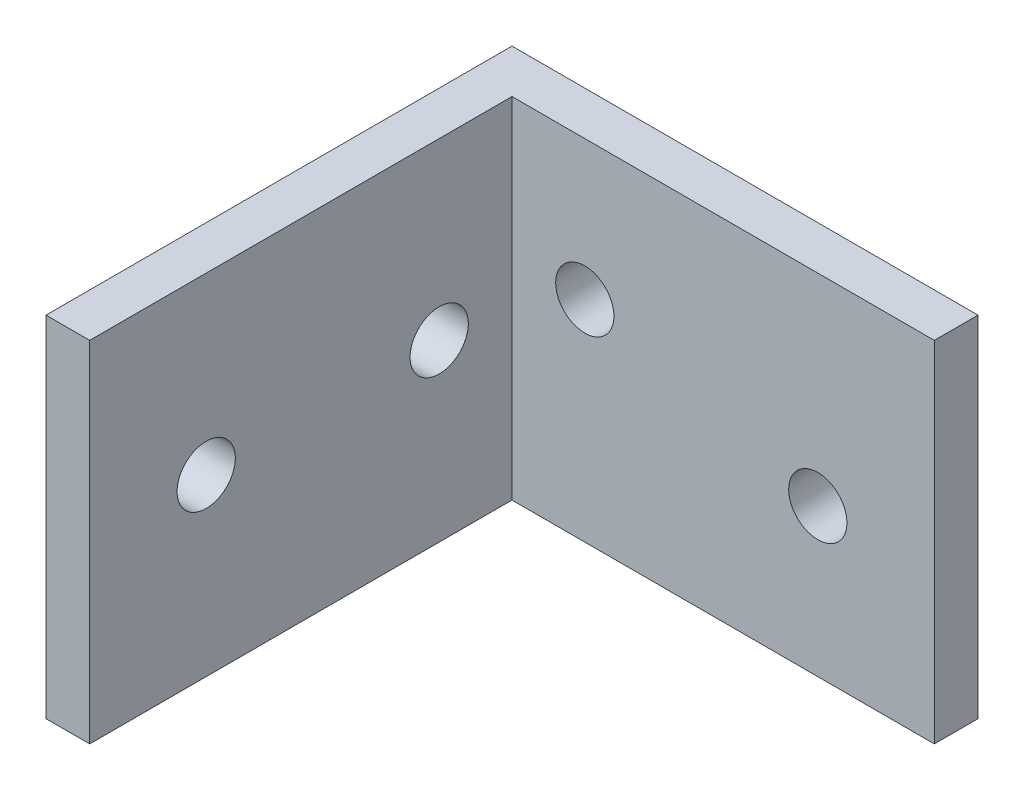
SolidWorks part; units mm, degrees
material "6061 Alloy"
ref_plane "Front Plane" through (0, 0, 0) normal (0, 0, 1) x (1, 0, 0)
ref_plane "Top Plane" through (0, 0, 0) normal (0, 1, 0) x (1, 0, 0)
ref_plane "Right Plane" through (0, 0, 0) normal (1, 0, 0) x (0, 0, -1)
sketch "Sketch1" plane through (0, 0, 0) normal (0, 1, 0) x (1, 0, 0)
  line L0 (0, 0) -> (0, 50.8)
  line L1 (0, 50.8) -> (50.8, 50.8)
  line L2 (4.7625, 0) -> (4.7625, 46.0375)
  line L3 (4.7625, 46.0375) -> (50.8, 46.0375)
  line L4 (0, 0) -> (4.7625, 0)
  line L5 (50.8, 50.8) -> (50.8, 46.0375)
  dimension "D2" = 50.8
  dimension "D3" = 50.8
  dimension "D1" = 4.7625
extrude "Boss-Extrude1" add sketch "Sketch1" along normal blind 38.1
sketch "Sketch2" plane through (0, 0, -50.8) normal (0, 0, -1) x (-1, 0, 0)
  line L0 (0, 26.3118) -> (-50.8, 12.7) construction
  line L1 (0, 38.1) -> (0, 0) construction
  line L2 (-50.8, 38.1) -> (-50.8, 0) construction
  line L3 (-50.8, 0) -> (0, 0) construction
  line L4 (-50.8, 38.1) -> (0, 38.1) construction
  circle A0 centre (-12.7, 22.9089) radius 3.175
  circle A1 centre (-38.1, 16.103) radius 3.175
  dimension "D3" = 6.35
  dimension "D4" = 6.35
  dimension "D5" = 12.7
  dimension "D6" = 25.4
  dimension "D1" = 12.7
  dimension "D2" = 15
extrude "Cut-Extrude1" cut sketch "Sketch2" against normal up to next
sketch "Sketch4" plane through (0, 0, 0) normal (-1, 0, 0) x (0, 0, 1)
  line L0 (0, 38.1) -> (0, 0) construction
  line L1 (-50.8, 38.1) -> (0, 38.1) construction
  circle A0 centre (-12.7, 19.05) radius 3.175
  circle A1 centre (-38.1, 19.05) radius 3.175
  dimension "D1" = 6.35
  dimension "D2" = 6.35
  dimension "D3" = 12.7
  dimension "D4" = 19.05
  dimension "D5" = 19.05
  dimension "D6" = 25.4
extrude "Cut-Extrude2" cut sketch "Sketch4" against normal up to next
